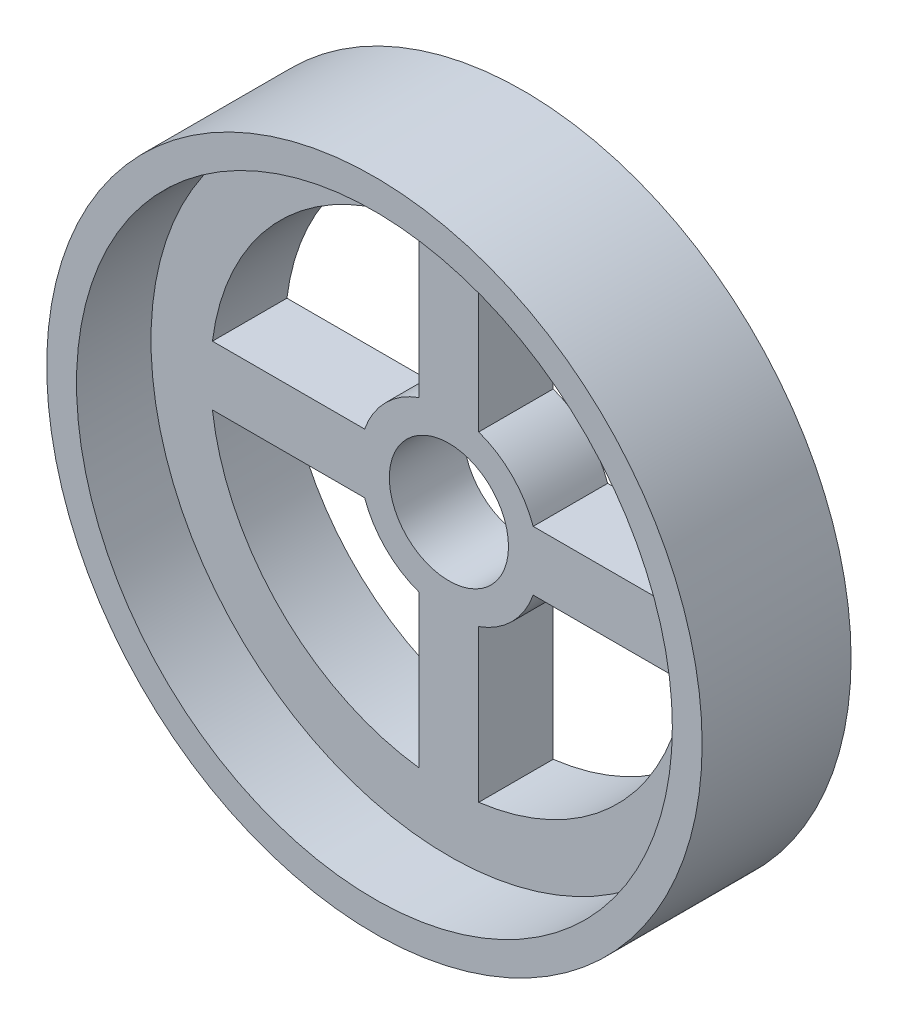
SolidWorks part; units mm, degrees
ref_plane "Plano frontal" through (0, 0, 0) normal (0, 0, 1) x (1, 0, 0)
ref_plane "Plano superior" through (0, 0, 0) normal (0, 1, 0) x (1, 0, 0)
ref_plane "Plano direito" through (0, 0, 0) normal (1, 0, 0) x (0, 0, -1)
sketch "Esboço1" plane through (0, 0, 0) normal (0, 0, 1) x (1, 0, 0)
  circle A0 centre (0, 0) radius 20
  circle A1 centre (0, 0) radius 4
  circle A2 centre (0, 0) radius 22
  dimension "D1" = 40
  dimension "D2" = 8
  dimension "D3" = 2
extrude "Ressalto-extrusão3" add sketch "Esboço1" along normal blind 5 contours A0 A1 region at (-19.4343, 0, 0)
extrude "Ressalto-extrusão4" add sketch "Esboço1<6>" along normal blind 10 contours A2 A0 region at (-21.3777, 0, 0)
sketch "Esboço1<6>" plane through (0, 0, 0) normal (0, 0, 1) x (1, 0, 0) same geometry as "Esboço1"
extrude "Ressalto-extrusão5" add sketch "Esboço1<7>" along normal blind 2 contours A1 region at (0, 0, 0)
sketch "Esboço1<7>" plane through (0, 0, 0) normal (0, 0, 1) x (1, 0, 0) same geometry as "Esboço1"
sketch "Esboço2" plane through (0, 0, 5) normal (0, 0, 1) x (1, 0, 0)
  circle A0 centre (0, 0) radius 16
  dimension "D1" = 32
extrude "Corte-extrusão1" cut sketch "Esboço2" against normal blind 60
sketch "Esboço3" plane through (0, 0, 0) normal (0, 0, 1) x (1, 0, 0)
  line L2 (2, -15.8745) -> (2, -5.6569)
  line L4 (-2, -15.8745) -> (-2, -5.6569)
  line L5 (1.864, -15.8911) -> (0.699, -5.9591) construction
  line L7 (15.8748, -1.9973) -> (5.6578, -1.9973)
  line L9 (15.8748, 1.9973) -> (5.6578, 1.9973)
  line L20 (2, 5.6569) -> (2, 15.8745)
  line L22 (-0.699, 5.9591) -> (-1.864, 15.8911) construction
  line L23 (-2, 5.6569) -> (-2, 15.8745)
  line L24 (-5.6578, 1.9973) -> (-15.8748, 1.9973)
  line L25 (-5.9538, 0.7432) -> (-15.8768, 1.9819) construction
  line L26 (-5.6578, -1.9973) -> (-15.8748, -1.9973)
  arc A0 (-5.6578, -1.9973) -> (-2, -5.6569) centre (0, 0) ccw
  circle A1 centre (0, 0) radius 4
  circle A2 centre (0, 0) radius 16 construction
  arc A3 (2, 15.8745) -> (-2, 15.8745) centre (0, 0) ccw
  arc A4 (-15.8748, 1.9973) -> (-15.8748, -1.9973) centre (0, 0) ccw
  arc A5 (15.8748, -1.9973) -> (15.8748, 1.9973) centre (0, 0) ccw
  arc A6 (-2, -15.8745) -> (2, -15.8745) centre (0, 0) ccw
  arc A7 (2, -5.6569) -> (5.6578, -1.9973) centre (0, 0) ccw
  arc A8 (5.6578, 1.9973) -> (2, 5.6569) centre (0, 0) ccw
  arc A9 (-2, 5.6569) -> (-5.6578, 1.9973) centre (0, 0) ccw
  dimension "D1" = 8
  dimension "D2" = 2
extrude "Ressalto-extrusão6" add sketch "Esboço3" along normal blind 5
